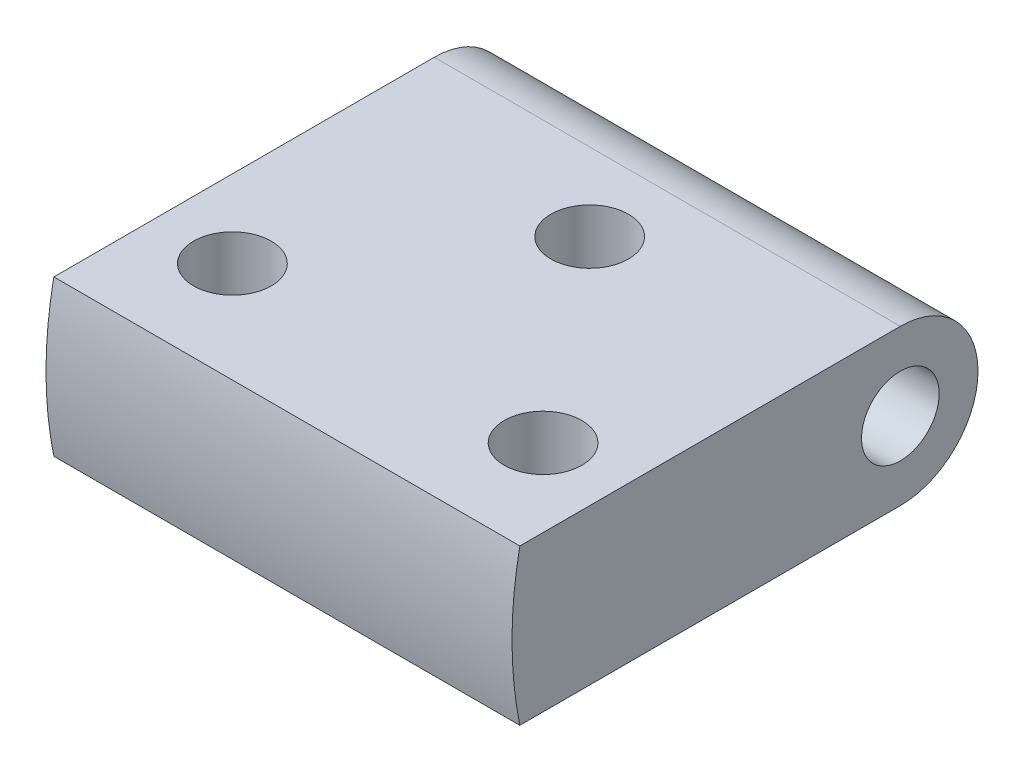
SolidWorks part; units mm, degrees
ref_plane "Front Plane" through (0, 0, 0) normal (0, 0, 1) x (1, 0, 0)
ref_plane "Top Plane" through (0, 0, 0) normal (0, 1, 0) x (1, 0, 0)
ref_plane "Right Plane" through (0, 0, 0) normal (1, 0, 0) x (0, 0, -1)
sketch "Sketch1" plane through (0, 0, 0) normal (0, 1, 0) x (1, 0, 0)
  line L1 (-15, -15) -> (15, -15)
  line L2 (-15, -15) -> (-15, 15)
  line L3 (-15, 15) -> (15, 15)
  line L4 (15, -15) -> (15, 15)
  line L5 (-15, -15) -> (15, 15) construction
  line L6 (-15, 15) -> (15, -15) construction
  point P0 (0, 0)
  dimension "D1" = 30
  dimension "D2" = 30
extrude "Boss-Extrude1" add sketch "Sketch1" along normal blind 10
fillet "Fillet1" radius 5 2 edges at (0, 0, -15) (0, 10, -15)
hole_wizard "CBORE for M5 Hex Head Bolt2" positions "Sketch2" profile "Sketch4" counterbore size "M5" standard "ANSI Metric" end condition up to next
sketch "Sketch2" plane through (15, 0, 0) normal (1, 0, 0) x (0, 0, -1)
  line L0 (10, 10) -> (10, 0)
  point P6 (10, 5)
sketch "Sketch4" plane through (15, 5, -10) normal (0, 1, 0) x (0, 0, -1)
  line L0 (0, 0) -> (0, 30)
  line L1 (0, 30) -> (2.25, 30)
  line L3 (2.25, 30) -> (2.25, 4.2)
  line L4 (2.25, 4.2) -> (2.5, 4.2)
  line L5 (2.5, 4.2) -> (2.5, 0)
  line L7 (2.5, 0) -> (0, 0)
  line L11 (0, -6.35) -> (0, 107.95) construction
  dimension "Thru Hole Dia." = 4.5
  dimension "Thru Hole Depth" = 30
  dimension "C'Bore Dia." = 5
  dimension "C'Bore Depth" = 4.2
hole_wizard "CBORE for M5 Hex Head Bolt1" positions "Sketch7" profile "Sketch8" counterbore size "M5" standard "ANSI Metric" end condition up to next
sketch "Sketch7" plane through (0, 10, 0) normal (0, 1, 0) x (1, 0, 0)
  line L0 (-10, -8) -> (10, -8)
  point P0 (-10, -8)
  point P1 (10, -8)
  point P4 (0, -8)
  point P7 (0, 5)
  point P9 (0, 0)
  dimension "D1" = 20
  dimension "D2" = 7
  dimension "D3" = 5
sketch "Sketch8" plane through (-10, 10, 8) normal (1, 0, 0) x (0, 0, 1)
  line L0 (0, 0) -> (0, 10)
  line L1 (0, 10) -> (2.25, 10)
  line L3 (2.25, 10) -> (2.25, 4.2)
  line L4 (2.25, 4.2) -> (2.5, 4.2)
  line L5 (2.5, 4.2) -> (2.5, 0)
  line L7 (2.5, 0) -> (0, 0)
  line L11 (0, -6.35) -> (0, 107.95) construction
  dimension "Thru Hole Dia." = 4.5
  dimension "Thru Hole Depth" = 10
  dimension "C'Bore Dia." = 5
  dimension "C'Bore Depth" = 4.2
sketch "Sketch9" plane through (15, 0, 0) normal (1, 0, 0) x (0, 0, -1)
  line L1 (35, 0) -> (-15, 0)
  line L2 (35, 0) -> (35, 10)
  line L3 (35, 10) -> (-15, 10)
  line L4 (-15, 0) -> (-15, 10)
  line L5 (35, 0) -> (-15, 10) construction
  line L6 (35, 10) -> (-15, 0) construction
  circle A0 centre (10, 5) radius 25
  line M7 (-15, 0) -> (10, 0)
  line M11 (-15, 10) -> (-15, 0)
extrude "Cut-Extrude1" cut sketch "Sketch9" against normal through all contours A0 L3 M11 | A0 L4 M7 region at (15, 1.2475, 14.8487) region at (15, 8.7525, 14.8487)
mirror "Mirror1" about plane through (0, 0, 0) normal (1, 0, 0) of "CBORE for M5 Hex Head Bolt2"
